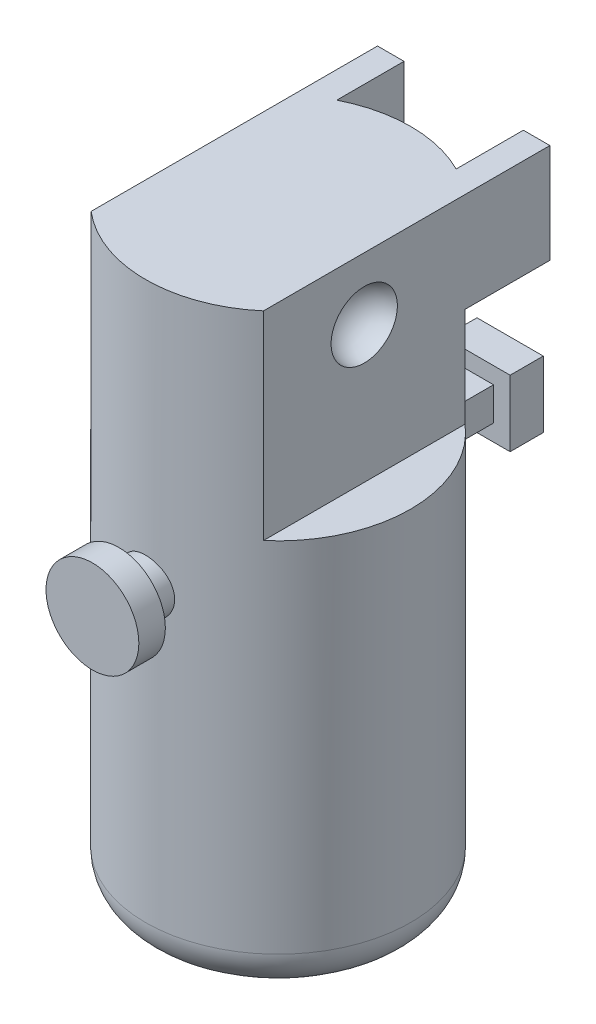
SolidWorks part; units mm, degrees
ref_plane "Front Plane" through (0, 0, 0) normal (0, 0, 1) x (1, 0, 0)
ref_plane "Top Plane" through (0, 0, 0) normal (0, 1, 0) x (1, 0, 0)
ref_plane "Right Plane" through (0, 0, 0) normal (1, 0, 0) x (0, 0, -1)
sketch "Sketch1" plane through (0, 0, 0) normal (0, 1, 0) x (1, 0, 0)
  circle A0 centre (0, 0) radius 10
  dimension "D1" = 20
extrude "Boss-Extrude2" add sketch "Sketch1" along normal blind 45 contours A0
ref_plane "Plane1" through (0, 45, 0) normal (0, 1, 0) x (1, 0, 0)
sketch "Sketch4" plane through (0, 45, 0) normal (0, 1, 0) x (1, 0, 0)
  line L1 (-6.5, -10) -> (6.5, -10)
  line L2 (-6.5, -10) -> (-6.5, 10)
  line L3 (-6.5, 10) -> (6.5, 10)
  line L4 (6.5, -10) -> (6.5, 10)
  line L5 (-6.5, -10) -> (6.5, 10) construction
  line L6 (-6.5, 10) -> (6.5, -10) construction
  point P0 (0, 0)
  dimension "D1" = 20
  dimension "D2" = 13
extrude "Cut-Extrude2" cut sketch "Sketch4" against normal blind 15 flip side to cut contours L2 L3 L4 L1
ref_plane "Plane3" through (-6.5, 0, 0) normal (-1, 0, 0) x (0, 0, 1)
sketch "Sketch5" plane through (-6.5, 0, 0) normal (-1, 0, 0) x (0, 0, 1)
  line L0 (-7.5993, 30) -> (-7.5993, 45) construction
  line L1 (7.5993, 30) -> (-7.5993, 30) construction
  line L3 (7.5993, 45) -> (7.5993, 30) construction
  line L4 (0, 42.7924) -> (0, 37.7924)
  arc A0 (0, 42.7924) -> (0, 37.7924) centre (0, 40.2924) ccw
  dimension "D1" = 2.5
  dimension "D2" = 7.5993
  dimension "D3" = 7.7924
  dimension "D4" = 7.5993
  dimension "D5" = 7.5993
revolve "Cut-Revolve1" cut sketch "Sketch5" angle 360 about L4
ref_plane "Plane5" through (6.5, 0, 0) normal (1, 0, 0) x (0, 0, -1)
ref_plane "Plane6" through (0, 0, 0) normal (1, 0, 0) x (0, 0, -1)
mirror "Mirror2" about plane through (0, 0, 0) normal (1, 0, 0) of "Cut-Revolve1"
fillet "Fillet2" radius 3 1 edges at (0, 0, 10)
ref_plane "Plane7" through (0, 0, -10) normal (0, 0, 1) x (1, 0, 0)
sketch "Sketch7" plane through (0, 0, -10) normal (0, 0, 1) x (1, 0, 0)
  line L0 (-7, 0) -> (7, 0) construction
  line L1 (-1.25, 23.75) -> (1.25, 23.75)
  line L2 (-1.25, 23.75) -> (-1.25, 26.25)
  line L3 (-1.25, 26.25) -> (1.25, 26.25)
  line L4 (1.25, 23.75) -> (1.25, 26.25)
  line L5 (-1.25, 23.75) -> (1.25, 26.25) construction
  line L6 (-1.25, 26.25) -> (1.25, 23.75) construction
  line L7 (-10, 30) -> (-10, 3) construction
  point P0 (0, 25)
  dimension "D1" = 2.5
  dimension "D2" = 2.5
  dimension "D3" = 25
  dimension "D4" = 10
extrude "Boss-Extrude3" add sketch "Sketch7" along normal up to surface and the other way blind 5 contours L2 L3 L4 L1 up to face at (0, 3, 10)
ref_plane "Plane8" through (0, 0, -15) normal (0, 0, -1) x (-1, 0, 0)
sketch "Sketch8" plane through (0, 0, -15) normal (0, 0, -1) x (-1, 0, 0)
  line L0 (10, 3) -> (10, 30) construction
  line L1 (-2.5, 22.5) -> (2.5, 22.5)
  line L2 (-2.5, 22.5) -> (-2.5, 27.5)
  line L3 (-2.5, 27.5) -> (2.5, 27.5)
  line L4 (2.5, 22.5) -> (2.5, 27.5)
  line L5 (-2.5, 22.5) -> (2.5, 27.5) construction
  line L6 (-2.5, 27.5) -> (2.5, 22.5) construction
  point P0 (0, 25)
  dimension "D1" = 5
  dimension "D2" = 5
  dimension "D3" = 10
  dimension "D4" = 25
extrude "Boss-Extrude4" add sketch "Sketch8" along normal blind 2.5
ref_plane "Plane9" through (0, 0, 10) normal (0, 0, 1) x (1, 0, 0)
sketch "Sketch9" plane through (0, 0, 10) normal (0, 0, 1) x (1, 0, 0)
  line L0 (-10, 30) -> (-10, 3) construction
  line L1 (6.5, 45) -> (-6.5, 45) construction
  circle A0 centre (0, 25) radius 2
  dimension "D3" = 4
  dimension "D1" = 10
  dimension "D2" = 20
extrude "Boss-Extrude6" add sketch "Sketch9" along normal blind 2 and the other way up to surface contours A0 other way up to face at (0, 25, -9.9608)
sketch "Sketch10" plane through (0, 0, 12) normal (0, 0, 1) x (1, 0, 0)
  line L0 (10, 3) -> (10, 30) construction
  line L1 (6.5, 45) -> (-6.5, 45) construction
  circle A0 centre (0, 24.9952) radius 3.5
  dimension "D3" = 7
  dimension "D1" = 10
  dimension "D2" = 20.0048
extrude "Boss-Extrude7" add sketch "Sketch10" along normal blind 2
sketch "Sketch11" plane through (6.5, 0, 0) normal (1, 0, 0) x (0, 0, -1)
  line L1 (14, 45) -> (14, 37.5)
  line L5 (14, 45) -> (7.5993, 45)
  line L6 (14, 37.5) -> (7.5993, 37.5)
  line L10 (7.5993, 45) -> (7.5993, 37.5)
  dimension "D1" = 7.5
  dimension "D2" = 6.4007
extrude "Boss-Extrude8" add sketch "Sketch11" against normal blind 2
mirror "Mirror3" about plane through (0, 0, 0) normal (1, 0, 0) of "Boss-Extrude8"
